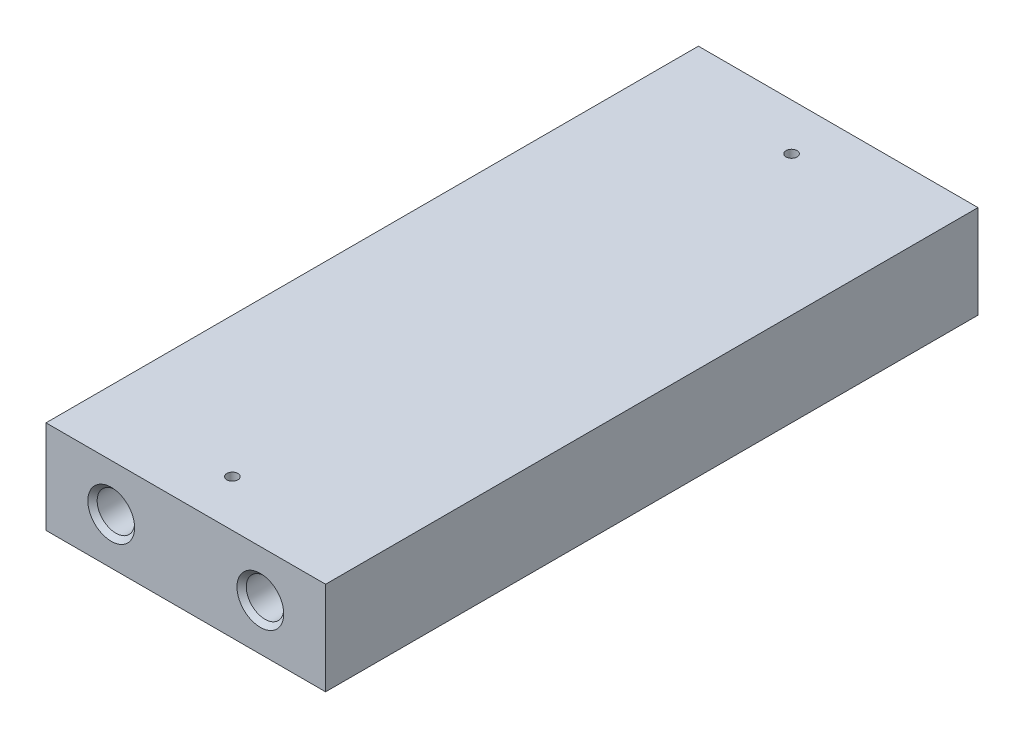
SolidWorks part; units mm, degrees
material "6063-T5"
ref_plane "Front Plane" through (0, 0, 0) normal (0, 0, 1) x (1, 0, 0)
ref_plane "Top Plane" through (0, 0, 0) normal (0, 1, 0) x (1, 0, 0)
ref_plane "Right Plane" through (0, 0, 0) normal (1, 0, 0) x (0, 0, -1)
sketch "Sketch1" plane through (0, 0, 0) normal (0, 0, 1) x (1, 0, 0)
  line L1 (-19.05, -6.35) -> (19.05, -6.35)
  line L2 (-19.05, -6.35) -> (-19.05, 6.35)
  line L3 (-19.05, 6.35) -> (19.05, 6.35)
  line L4 (19.05, -6.35) -> (19.05, 6.35)
  line L5 (-19.05, -6.35) -> (19.05, 6.35) construction
  line L6 (-19.05, 6.35) -> (19.05, -6.35) construction
  point P0 (0, 0)
  dimension "D1" = 38.1
  dimension "D2" = 12.7
extrude "Boss-Extrude1" add sketch "Sketch1" against normal blind 88.9
sketch "Sketch2" plane through (0, 0, 0) normal (0, 0, 1) x (1, 0, 0)
  line L1 (0, -1000) -> (0, 49000) construction
  point P0 (-10.16, 0)
  point P1 (10.16, 0)
  dimension "D1" = 20.32
hole_wizard "1/4-20 Tapped Hole1" positions "3DSketch1" profile "Sketch4" tap size "1/4-20" standard "ANSI Inch"
sketch3d "3DSketch1"
  point P0 (-10.16, 0, 0)
  point P3 (10.16, 0, 0)
sketch "Sketch4" plane through (-10.16, 0, 0) normal (1, 0, 0) x (0, -1, 0)
  line L0 (0, 0) -> (0, 18.0438)
  line L1 (0, 18.0438) -> (2.5527, 16.51)
  line L2 (2.5527, 16.51) -> (2.5527, 0.635)
  line L3 (2.5527, 0.635) -> (3.1877, 0)
  line L5 (3.1877, 0) -> (0, 0)
  line L6 (-2.5527, 0.635) -> (-3.1877, 0) construction
  line L10 (0, 18.0438) -> (-2.5527, 16.51) construction
  line L11 (0, -6.35) -> (0, 107.95) construction
  dimension "Tap Drill Dia." = 5.1054
  dimension "Tap Drill Depth" = 16.51
  dimension "Near C'Sink Dia." = 6.3754
  dimension "Near C'Sink Angle" = 90
  dimension "Drill Angle" = 118
cosmetic thread "Hole Thread1" parameters "D1"=12.7, "D2"=6.35
cosmetic thread "Hole Thread2" parameters "D1"=12.7, "D2"=6.35
ref_plane "Plane1" through (0, 0, -44.45) normal (0, 0, 1) x (1, 0, 0)
mirror "Mirror1" about plane through (0, 0, -44.45) normal (0, 0, 1) of "1/4-20 Tapped Hole1"
sketch "Sketch5" plane through (0, 6.35, 0) normal (0, 1, 0) x (1, 0, 0)
  line L0 (0, -1000) -> (0, 49000) construction
  line L1 (-999.1252, 44.45) -> (49000.8748, 44.45) construction
  line L3 (19.05, 0) -> (-19.05, 0) construction
  line L4 (19.05, 88.9) -> (-19.05, 88.9) construction
  point P4 (0, 82.55)
  point P6 (0, 6.35)
  point P11 (0, 0)
  dimension "D1" = 76.2
hole_wizard "#1-64 Tapped Hole1" positions "3DSketch2" profile "Sketch7" tap size "#1-64" standard "ANSI Inch" end condition through all
sketch3d "3DSketch2"
  point P0 (0, 6.35, -82.55)
  point P3 (0, 6.35, -6.35)
sketch "Sketch7" plane through (0, 6.35, -82.55) normal (1, 0, 0) x (0, 0, 1)
  line L0 (0, 0) -> (0, 12.7)
  line L1 (0, 12.7) -> (0.7556, 12.7)
  line L2 (0.7556, 12.7) -> (0.7556, 0)
  line L5 (0.7556, 0) -> (0, 0)
  line L11 (0, -6.35) -> (0, 107.95) construction
  dimension "Thru Tap Drill Dia." = 1.5113
  dimension "Thru Tap Drill Depth" = 12.7
cosmetic thread "Hole Thread3" parameters "D2"=1.8542
cosmetic thread "Hole Thread4" parameters "D2"=1.8542
